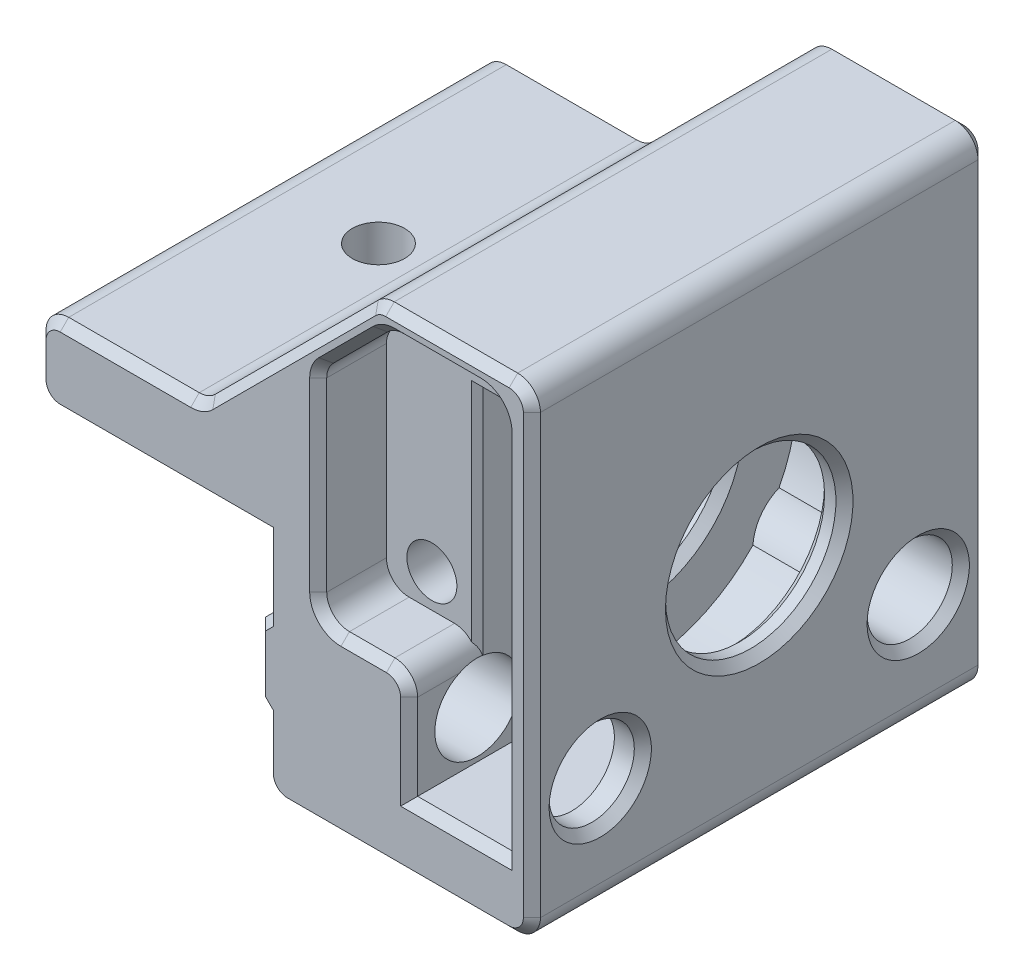
SolidWorks part; units mm, degrees
ref_plane "Front" through (0, 0, 0) normal (0, 0, 1) x (1, 0, 0)
ref_plane "Top" through (0, 0, 0) normal (0, 1, 0) x (1, 0, 0)
ref_plane "Right" through (0, 0, 0) normal (1, 0, 0) x (0, 0, -1)
sketch "Skizze2" plane through (0, 0, 0) normal (0, 0, 1) x (1, 0, 0)
  line L0 (0, -20) -> (0, 0)
  line L1 (0, 0) -> (-20, 0)
  line L2 (-20, 0) -> (-20, 7)
  line L3 (-20, 7) -> (-5.6885, 7)
  line L5 (13.2349, -20) -> (0, -20)
  line L6 (-5.6885, 7) -> (9.8115, 22.5)
  line L7 (9.8115, 22.5) -> (23.5, 22.5)
  line L8 (24, -6) -> (24, 6) construction
  line L9 (21, 14) -> (13, 14) construction
  line L10 (13.2349, -20) -> (23.5, -20)
  line L11 (107.5, -20) -> (2.5, -20) construction
  line L12 (23.5, -20) -> (23.5, 22.5)
  dimension "D1" = 20
  dimension "D2" = 7
  dimension "D3" = 0.5
  dimension "D4" = 45
  dimension "D5" = 8.5
extrude "Aufsatz-Linear austragen1" add sketch "Skizze2" along normal blind 40
sketch "Skizze7" plane through (0, 0, 40) normal (0, 0, 1) x (1, 0, 0)
  line L0 (0, 0) -> (28.9535, 0) construction
  line L1 (21, -14.15) -> (21, 14.15)
  line L2 (21, -14) -> (21, 14) construction
  line L3 (21, 14.15) -> (12.7, 14.15)
  line L4 (12.7, 14.15) -> (12.7, -14.15)
  line L5 (21, -14.15) -> (12.7, -14.15)
  point P9 (12.7, 0)
  point P11 (21, 0)
  dimension "D1" = 28.3
  dimension "D2" = 8.3
extrude "Schnitt-Linear austragen3" cut sketch "Skizze7" against normal up to surface (20 mm away)
sketch "Skizze8" plane through (21, 0, 0) normal (-1, 0, 0) x (0, 0, 1)
  line L0 (20, -14.15) -> (20, 14.15) construction
  line L1 (20, -14.15) -> (20, 14.15)
  arc A0 (20, 14.15) -> (20, -14.15) centre (20, 0) ccw
extrude "Schnitt-Linear austragen4" cut sketch "Skizze8" along normal up to surface (8.3 mm away) up to face at (12.7, 0, 30)
sketch "Skizze9" plane through (21, 0, 0) normal (-1, 0, 0) x (0, 0, 1)
  circle A0 centre (20, 0) radius 7.5
  dimension "D1" = 15
extrude "Schnitt-Linear austragen5" cut sketch "Skizze9" against normal blind 18
sketch "Skizze14" plane through (0, 0, 40) normal (0, 0, 1) x (1, 0, 0)
  line L0 (0, -10) -> (-13.7327, -10) construction
  line L1 (0, 0) -> (0, -20) construction
  line L2 (0, -13.5) -> (0, -6.5)
  line L3 (0, -6.5) -> (-0.7, -7.2)
  line L4 (-0.7, -7.2) -> (-0.7, -12.8)
  line L5 (0, -13.5) -> (-0.7, -12.8)
  point P9 (-0.7, -10)
  dimension "D1" = 0.7
  dimension "D2" = 7
  dimension "D3" = 45
extrude "Aufsatz-Linear austragen2" add sketch "Skizze14" against normal up to surface (40 mm away) up to face at (1.3904, 2.375, 0)
sketch "Skizze10" plane through (12.7, 0, 0) normal (1, 0, 0) x (0, 0, -1)
  circle A0 centre (-20, 0) radius 8.65
  dimension "D1" = 17.3
extrude "Schnitt-Linear austragen6" cut sketch "Skizze10" against normal offset from surface (16.2 mm away) 3.5 up to face at (0, -16.75, 20) offset beyond the face yes
sketch "Skizze11" plane through (0, 0, 0) normal (-1, 0, 0) x (0, 0, 1)
  line L0 (40, -10) -> (0, -10) construction
  line L1 (40, 0) -> (40, -6.5) construction
  line L2 (0, 0) -> (0, -6.5) construction
  line L3 (40, -20) -> (0, -20) construction
  line L4 (20, -20) -> (20, -13.458) construction
  circle A0 centre (33.9892, -10) radius 2.3
  circle A1 centre (33.9892, -10) radius 3.75
  circle A2 centre (6.0108, -10) radius 3.75
  circle A3 centre (6.0108, -10) radius 2.3
  dimension "D2" = 4.6
  dimension "D3" = 7.5
  dimension "D1" = 10
extrude "Schnitt-Linear austragen7" cut sketch "Skizze11" against normal up to next and the other way blind 7 contours L0 A0 | A0 L0 | A3 region at (0, -10, 33.9892) region at (0, -10, 6.0108)
extrude "Schnitt-Linear austragen8" cut sketch "Skizze11<3>" along normal offset from surface 7 and the other way through all from surface contours L0 A1 A0 | A1 L0 A0 | A0 L0 | L0 A0 | A2 A3 region at (0, -10, 33.9892) region at (0, -10, 30.3452) region at (0, -10, 2.3669) up to face at (0, -3.3294, 33.7647) starting at face at (12.7, -10, 36.2892)
sketch "Skizze11<3>" plane through (0, 0, 0) normal (-1, 0, 0) x (0, 0, 1) same geometry as "Skizze11"
sketch "Skizze12" plane through (0, 0, 0) normal (0, -1, 0) x (1, 0, 0)
  line L0 (-10, 40) -> (-10, 0) construction
  line L1 (-20, 40) -> (0, 40) construction
  line L2 (-20, 0) -> (0, 0) construction
  line L3 (-10, 20) -> (-20, 20) construction
  line L4 (-20, 40) -> (-20, 0) construction
  circle A1 centre (-10, 20) radius 2.3
  dimension "D1" = 4.6
extrude "Schnitt-Linear austragen9" cut sketch "Skizze12" against normal blind 7
sketch "Skizze15" plane through (0, 0, 0) normal (-1, 0, 0) x (0, 0, 1)
  circle A0 centre (6.0108, -10) radius 4.15
  circle A1 centre (33.9892, -10) radius 4.15
  dimension "D1" = 8.3
extrude "Schnitt-Linear austragen10" cut sketch "Skizze15" along normal blind 7
sketch "Skizze17" plane through (0, 0, 40) normal (0, 0, 1) x (1, 0, 0)
  line L0 (12.7, -4.5987) -> (4.7, -4.5987)
  line L1 (12.7, -6.5375) -> (12.7, 14.15) construction
  line L2 (4.7, -4.5987) -> (4.7, 14.5601)
  line L3 (4.7, 14.5601) -> (10.6399, 20.5)
  line L4 (10.6399, 20.5) -> (21, 20.5)
  line L5 (21, 20.5) -> (21, 14.15)
  line L7 (9.8115, 22.5) -> (-5.6885, 7) construction
  line L8 (12.7, -4.5987) -> (21, 14.15)
  line L9 (12.7, 14.15) -> (12.7, -14.15) construction
  line L10 (23.5, 22.5) -> (9.8115, 22.5) construction
  dimension "D1" = 2
  dimension "D2" = 2
  dimension "D3" = 8
extrude "Schnitt-Linear austragen11" cut sketch "Skizze17" against normal blind 6
sketch "Skizze18" plane through (0, 0, 34) normal (0, 0, 1) x (1, 0, 0)
  line L0 (8.7, -4.5987) -> (8.7, 9.672) construction
  line L1 (4.7, -4.5987) -> (12.7, -4.5987) construction
  line L2 (16.85, 14.15) -> (16.85, 20.5) construction
  line L3 (21, 14.15) -> (12.7, 14.15) construction
  line L4 (21, 20.5) -> (10.6399, 20.5) construction
  circle A0 centre (16.85, 17.325) radius 2.2
  circle A1 centre (8.7, -1.6589) radius 2.2
  dimension "D1" = 4.4
extrude "Schnitt-Linear austragen12" cut sketch "Skizze18" against normal blind 6
fillet "Verrundung1" radius 2 14 edges at (4.7, 14.5601, 37) (12.7, -4.5987, 37) (4.7, -4.5987, 37) (-1.75, 0, 11.35) (-1.75, 0, 28.65) (0, -20, 20) (23.5, -20, 20) (23.5, 22.5, 20) (21, 20.5, 37) (10.6399, 20.5, 37) (9.8115, 22.5, 20) (-20, 0, 20) (-20, 7, 20) (-5.6885, 7, 20)
chamfer "Fase1" distance 0.75 angle 45 58 edges at (-0.35, -13.15, 40) (-0.7, -10, 40) (-0.35, -6.85, 40) (0, -3.25, 40) (-9, 0, 40) (-19.4142, 0.5858, 40) (-20, 3.5, 40) (-19.4142, 6.4142, 40) (-12.2585, 7, 40) (2.0615, 14.75, 40) (9.8746, 22.3478, 40) (16.07, 22.5, 40) (22.9142, 21.9142, 40) (23.5, 1.25, 40) (22.9142, -19.4142, 40) (11.75, -20, 40) (0.5858, -19.4142, 40) (0, -15.75, 40) (16.85, -14.15, 40) (21, 2.175, 40) (20.4142, 19.9142, 40) (15.2342, 20.5, 40) (10.703, 20.3478, 40) (7.67, 17.53, 40) (4.8522, 14.497, 40) (4.7, 5.5665, 40) (5.2858, -4.0129, 40) (8.7, -4.5987, 40) (12.1142, -5.1844, 40) (12.7, -10.3743, 40) (22.9142, -19.4142, 0) (23.5, 1.25, 0) (22.9142, 21.9142, 0) (16.07, 22.5, 0) (9.8746, 22.3478, 0) (2.0615, 14.75, 0) (-12.2585, 7, 0) (-19.4142, 6.4142, 0) (-20, 3.5, 0) (-19.4142, 0.5858, 0) (-9, 0, 0) (0, -3.25, 0) (-0.35, -6.85, 0) (-0.7, -10, 0) (-0.35, -13.15, 0) (0, -15.75, 0) (0.5858, -19.4142, 0) (11.75, -20, 0) (23.5, -10, 37.7392) (23.5, -10, 9.7608) (12.7, 0, 11.35) (21, 0, 27.5) (23.5, 0, 27.5) (-3.5, 0, 20) (0, -2.8084, 28.1814) (0, -2.8084, 11.8186) (-5.7516, 7.1522, 40) (-5.7516, 7.1522, 0)
chamfer "Fase2" distance 0.5 angle 45 2 edges at (16.85, 14.15, 34) (12.7, 3.95, 34)
fillet "Verrundung2" radius 0.75 4 edges at (-0.7, -10, 38.1392) (-0.7, -10, 29.8392) (-0.7, -10, 1.8608) (-0.7, -10, 10.1608)
